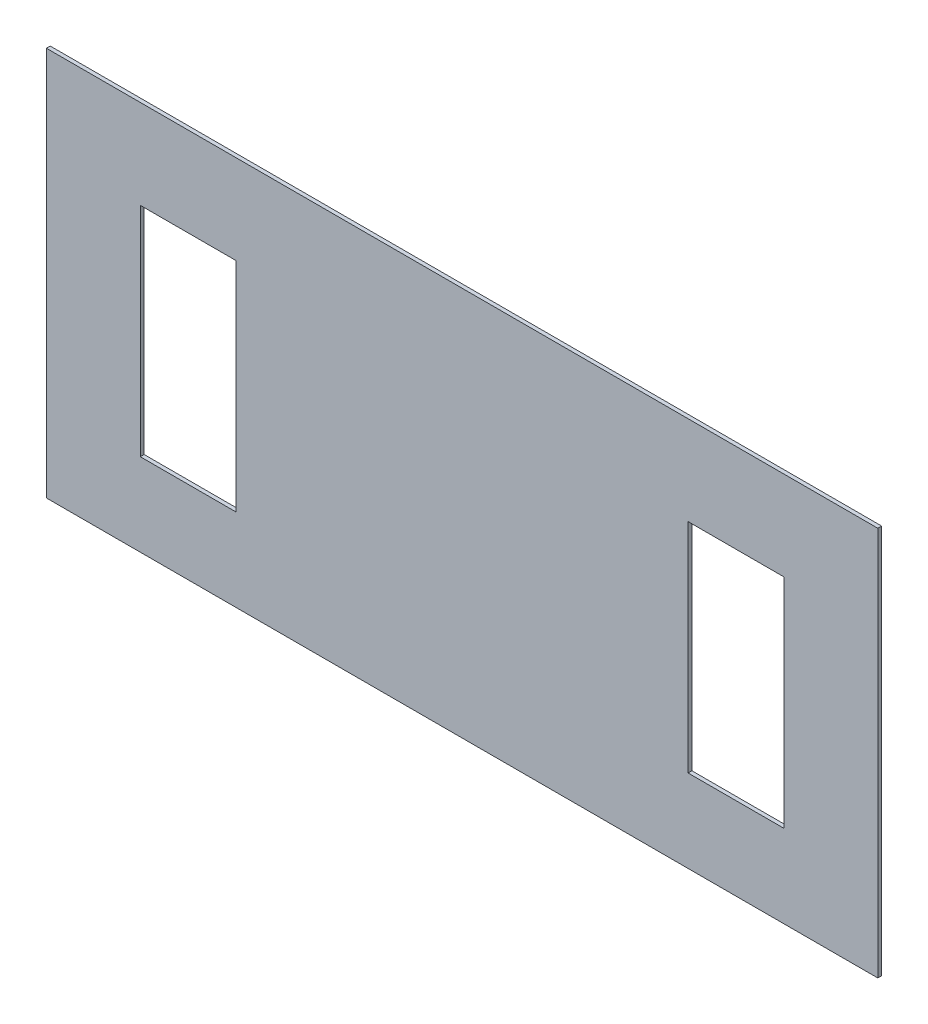
SolidWorks part; units mm, degrees
ref_plane "Front Plane" through (0, 0, 0) normal (0, 0, 1) x (1, 0, 0)
ref_plane "Top Plane" through (0, 0, 0) normal (0, 1, 0) x (1, 0, 0)
ref_plane "Right Plane" through (0, 0, 0) normal (1, 0, 0) x (0, 0, -1)
sketch "Sketch1" plane through (0, 0, 0) normal (0, 0, 1) x (1, 0, 0)
  line L0 (-11.525, -100) -> (-11.525, 103.337)
  line L1 (-11.525, 103.337) -> (422.475, 103.337)
  line L2 (422.475, 103.337) -> (422.475, -100)
  line L3 (422.475, -100) -> (-11.525, -100)
extrude "Boss-Extrude1" add sketch "Sketch1" along normal blind 2
sketch "Sketch2" plane through (0, 0, 2) normal (0, 0, 1) x (1, 0, 0)
  line L0 (205.475, -100) -> (205.475, 103.337) construction
  line L1 (87.4914, -56.8268) -> (37.4914, -56.8268)
  line L2 (87.4914, -56.8268) -> (87.4914, 56.8268)
  line L3 (87.4914, 56.8268) -> (37.4914, 56.8268)
  line L4 (37.4914, -56.8268) -> (37.4914, 56.8268)
  line L5 (87.4914, -56.8268) -> (37.4914, 56.8268) construction
  line L6 (87.4914, 56.8268) -> (37.4914, -56.8268) construction
  line L7 (-11.525, -100) -> (422.475, -100) construction
  line L8 (422.475, 103.337) -> (-11.525, 103.337) construction
  line L9 (323.4586, 56.8268) -> (373.4586, -56.8268) construction
  line L10 (323.4586, -56.8268) -> (373.4586, 56.8268) construction
  line L11 (373.4586, -56.8268) -> (373.4586, 56.8268)
  line L12 (323.4586, 56.8268) -> (373.4586, 56.8268)
  line L13 (323.4586, -56.8268) -> (323.4586, 56.8268)
  line L14 (323.4586, -56.8268) -> (373.4586, -56.8268)
  point P0 (62.4914, 0)
  point P15 (348.4586, 0)
  point P16 (76.025, 1.9832)
  point P17 (64.9754, 4.1386)
  point P18 (0, 0)
  point P19 (0, 0)
  point P20 (64.027, 2.4684)
  point P21 (62.4914, 4.1172)
  point P22 (64.0393, 2.0483)
  point P23 (0, 0)
  point P24 (62.4914, 0)
  dimension "D1" = 50
extrude "Cut-Extrude1" cut sketch "Sketch2" against normal through all
